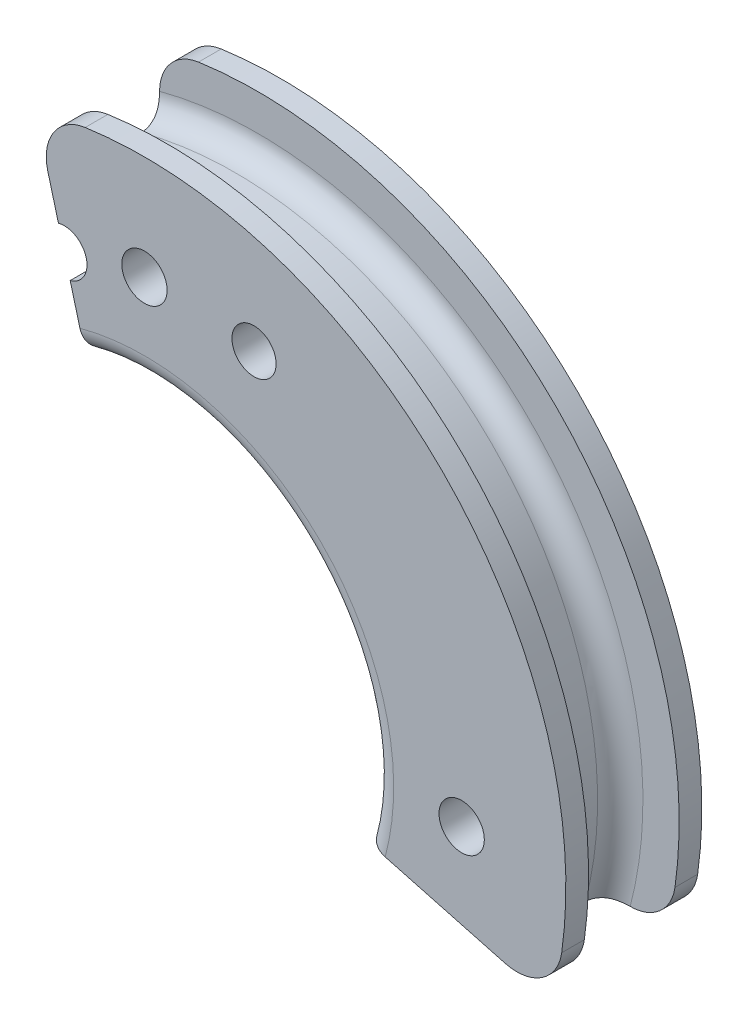
SolidWorks part; units mm, degrees
ref_plane "Front" through (0, 0, 0) normal (0, 0, 1) x (1, 0, 0)
ref_plane "Top" through (0, 0, 0) normal (0, 1, 0) x (1, 0, 0)
ref_plane "Right" through (0, 0, 0) normal (1, 0, 0) x (0, 0, -1)
sketch "Sketch1" plane through (0, 0, 0) normal (0, 0, 1) x (1, 0, 0)
  line L0 (0, 7) -> (0, -7) construction
  circle A2 centre (7, 0) radius 0.5
  circle A24 centre (0, 0) radius 8.5
  circle A25 centre (0, 0) radius 5
  circle A30 centre (0, -7) radius 0.5
  circle A32 centre (-7, 0) radius 0.5
  circle A34 centre (0, 7) radius 0.5
  point P20 (0, 0)
  dimension "D1" = 4
  dimension "D2" = 17
  dimension "D3" = 10
  dimension "D4" = 14
extrude "Boss-Extrude1" add sketch "Sketch1" along normal mid plane 3
sketch "Sketch2" plane through (0, 0, 0) normal (0, 1, 0) x (1, 0, 0)
  line L1 (0, 0) -> (0, 3.24) construction
  line L2 (-8, 0.5) -> (-8, -0.5)
  line L3 (-8, 0) -> (-8.5, 0) construction
  line L4 (-8.5, 1.5) -> (-8.5, -1.5) construction
  line L5 (-8.5, -1) -> (-8.5, 1)
  arc A1 (-8.5, 1) -> (-8, 0.5) centre (-8.5, 0.5) cw
  arc A2 (-8.5, -1) -> (-8, -0.5) centre (-8.5, -0.5) ccw
  dimension "D1" = 2
  dimension "D2" = 16
revolve "Cut-Revolve1" cut sketch "Sketch2" angle 360 about L1
sketch "Sketch7" plane through (0, 0, 0) normal (0, 1, 0) x (1, 0, 0)
  line L0 (0, 0) -> (11.0142, 0) construction
  line L1 (8.5, 1.5) -> (9.3, 1.5)
  line L2 (8.5, 1.5) -> (8.5, 1)
  line L3 (8.5, 1) -> (9.3, 1)
  line L4 (9.3, 1.5) -> (9.3, 1)
  line L5 (9.3, -1.5) -> (9.3, -1)
  line L6 (8.5, -1) -> (9.3, -1)
  line L7 (8.5, -1.5) -> (8.5, -1)
  line L8 (8.5, -1.5) -> (9.3, -1.5)
  line L9 (8.5, 1) -> (-8.5, 1) construction
  line L10 (0, 0) -> (0, 2.6862) construction
  dimension "D1" = 0.8
revolve "Revolve1" add sketch "Sketch7" angle 360 about L10
sketch "Sketch4" plane through (0, 0, 0) normal (0, 0, 1) x (1, 0, 0)
  line L0 (-2.6543, 9.9058) -> (0, 0)
  line L1 (0, 0) -> (6.0104, 6.0104) construction
  line L2 (0, 0) -> (-16.6927, 0) construction
  line L3 (10.3501, -2.7733) -> (0, 0)
  line L5 (-2.6543, 9.9058) -> (-11.3342, 9.9058)
  line L6 (-11.3342, 9.9058) -> (-11.3342, -11.0336)
  line L7 (-11.3342, -11.0336) -> (10.3501, -11.0336)
  line L10 (10.3501, -2.7733) -> (10.3501, -11.0336)
  dimension "D3" = 60
  dimension "D1" = 135
  dimension "D2" = 120
extrude "Cut-Extrude1" cut sketch "Sketch4" against normal through all both and the other way through all
sketch "Sketch5" plane through (0, 0, 1.5) normal (0, 0, 1) x (1, 0, 0)
  line L0 (-1.2941, 4.8296) -> (-2.407, 8.9831) construction
  circle A0 centre (-1.7683, 6.5992) radius 0.5
  circle A1 centre (2.418, 6.7946) radius 0.4873
  dimension "D1" = 1
extrude "Cut-Extrude2" cut sketch "Sketch5" against normal through all both and the other way through all
fillet "Fillet1" radius 0.5 2 edges at (3.5355, 3.5355, 1.5) (3.5355, 3.5355, -1.5)
sketch "Sketch6" plane through (0, 0, 0) normal (0, 0, 1) x (1, 0, 0)
  circle A0 centre (0, 0) radius 8
  dimension "D1" = 16
fillet "Fillet2" radius 1 4 edges at (8.9831, -2.407, -1.25) (8.9831, -2.407, 1.25) (-2.407, 8.9831, -1.25) (-2.407, 8.9831, 1.25)
chamfer "Chamfer1" distance 1 angle 45 2 edges at (7.5, 0, -1.5) (2.9053, 6.7946, -1.5)
